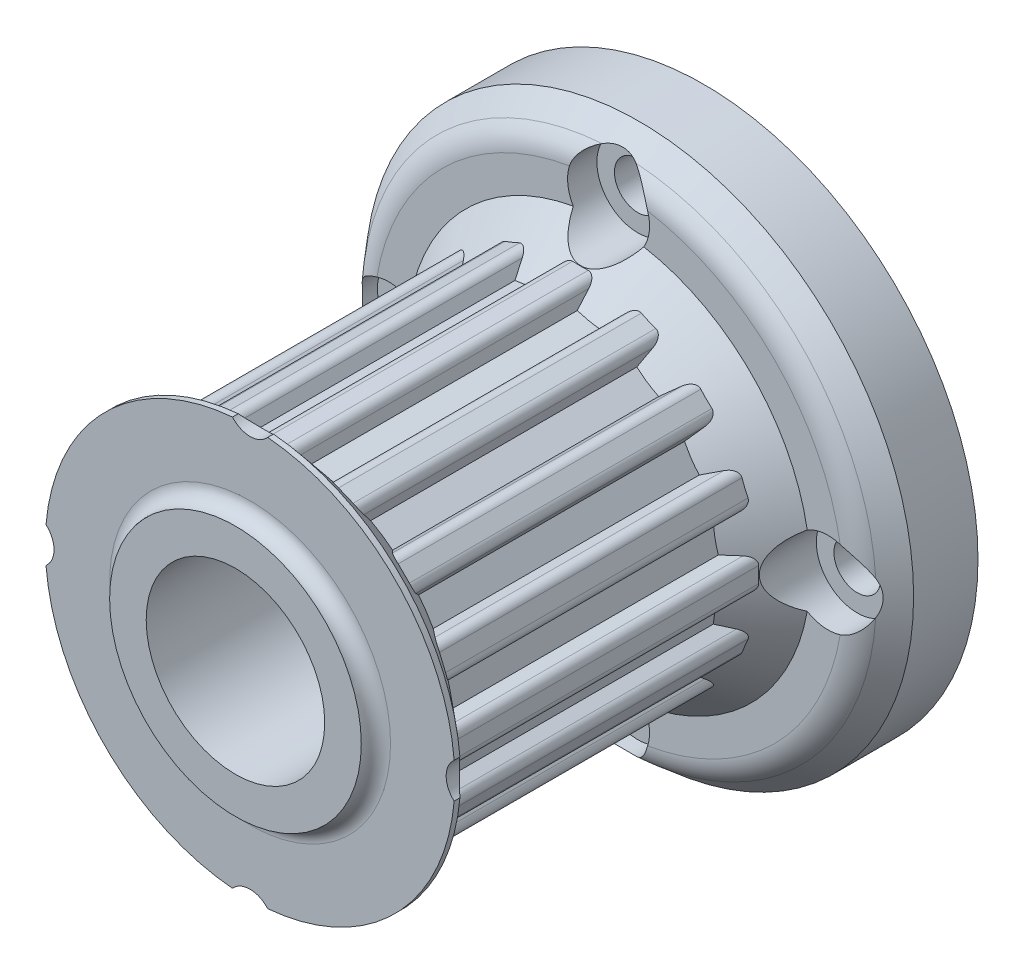
SolidWorks part; units mm, degrees
material "ABS"
ref_plane "Plan de face" through (0, 0, 0) normal (0, 0, 1) x (1, 0, 0)
ref_plane "Plan de dessus" through (0, 0, 0) normal (0, 1, 0) x (1, 0, 0)
ref_plane "Plan de droite" through (0, 0, 0) normal (1, 0, 0) x (0, 0, -1)
sketch "Esquisse1" plane through (0, 0, 0) normal (0, 0, 1) x (1, 0, 0)
  circle A0 centre (0, 0) radius 14
  dimension "D1" = 28
extrude "Boss.-Extru.1" add sketch "Esquisse1" along normal blind 28
sketch "Esquisse2" plane through (0, 0, 0) normal (0, 0, -1) x (-1, 0, 0)
  circle A0 centre (0, 0) radius 8.25
  circle A1 centre (0, 0) radius 14
  circle A2 centre (0, 0) radius 14 construction
  dimension "D1" = 16.5
extrude "Enlèv. mat.-Extru.1" cut sketch "Esquisse2" against normal blind 3.5
sketch "Esquisse3" plane through (0, 0, 0) normal (1, 0, 0) x (0, 0, -1)
  line L0 (-3.5, 14) -> (-28, 14) construction
  line L1 (-24.25, 14) -> (-7.25, 14)
  line L2 (-24.25, 14) -> (-24.25, 7.73)
  line L3 (-24.25, 7.73) -> (-7.25, 7.73)
  line L4 (-7.25, 14) -> (-7.25, 7.73)
  line L5 (-24.25, 14) -> (-7.25, 7.73) construction
  line L6 (-24.25, 7.73) -> (-7.25, 14) construction
  line L7 (-15.75, -14) -> (-15.75, 14) construction
  line L8 (-28, -14) -> (-3.5, -14) construction
  line L9 (-15.75, 0) -> (0, 0) construction
  point P4 (-15.75, 10.865)
  point P11 (0, 0)
  point P12 (-15.75, 0)
  dimension "D1" = 17
  dimension "D2" = 7.73
revolve "Enlèvement de matière-Révolution1" cut sketch "Esquisse3" angle 360 about L9
sketch "Esquisse4" plane through (0, 0, 0) normal (0, 0, -1) x (-1, 0, 0)
  circle A0 centre (0, 0) radius 3
  dimension "D1" = 6
extrude "Enlèv. mat.-Extru.2" cut sketch "Esquisse4" against normal through all
chamfer "Chanfrein1" distance 4 angle 40 2 edges at (14, 0, 7.25) (14, 0, 24.25) first distance on face at (-14, 0, 3.5) first distance on face at (7.73, 0, 24.25)
ref_plane "Plan1" through (0, 0, 5.25) normal (0, 0, 1) x (1, 0, 0)
sketch "Esquisse5" plane through (0, 0, 5.25) normal (0, 0, 1) x (1, 0, 0)
  line L0 (0, 0) -> (0, 12.73) construction
  line L1 (0, 0) -> (4.8716, 11.761) construction
  line L2 (0, 12.1872) -> (0.5089, 12.1872)
  line L3 (1.1017, 11.6799) -> (1.2239, 10.8985)
  line L4 (1.2239, 10.8985) -> (2.9901, 10.5515)
  line L5 (2.9901, 10.5515) -> (3.3975, 11.2265)
  line L6 (4.1408, 11.4708) -> (4.6619, 11.2549)
  line L7 (0, 0) -> (2.107, 10.725) construction
  line L8 (4.6619, 11.2549) -> (5.1321, 11.0601)
  line L9 (5.4856, 10.3646) -> (5.2995, 9.5959)
  line L10 (5.2995, 9.5959) -> (6.7985, 8.5995)
  line L11 (6.7985, 8.5995) -> (7.4332, 9.0671)
  line L12 (8.2134, 9.0084) -> (8.6122, 8.6095)
  line L13 (8.6122, 8.6095) -> (8.9721, 8.2497)
  line L14 (9.0325, 7.4718) -> (8.5664, 6.8329)
  line L15 (8.5664, 6.8329) -> (9.57, 5.3386)
  line L16 (9.57, 5.3386) -> (10.3353, 5.5278)
  line L17 (11.0336, 5.1749) -> (11.2495, 4.6538)
  line L18 (11.2495, 4.6538) -> (11.4442, 4.1836)
  line L19 (11.2024, 3.4418) -> (10.5272, 3.03)
  line L20 (10.5272, 3.03) -> (10.8826, 1.2654)
  line L21 (10.8826, 1.2654) -> (11.6621, 1.1473)
  line L22 (12.1722, 0.554) -> (12.1722, -0.01)
  line L23 (12.1722, -0.01) -> (12.1722, -0.5189)
  line L24 (11.6649, -1.1117) -> (10.8835, -1.2339)
  line L25 (10.8835, -1.2339) -> (10.5365, -3.0001)
  line L26 (10.5365, -3.0001) -> (11.2115, -3.4075)
  line L27 (11.4558, -4.1508) -> (11.2399, -4.6719)
  line L28 (11.2399, -4.6719) -> (11.0452, -5.1421)
  line L29 (10.3496, -5.4957) -> (9.581, -5.3095)
  line L30 (9.581, -5.3095) -> (8.5845, -6.8085)
  line L31 (8.5845, -6.8085) -> (9.0522, -7.4432)
  line L32 (8.9934, -8.2234) -> (8.5946, -8.6222)
  line L33 (8.5946, -8.6222) -> (8.2347, -8.9821)
  line L34 (7.4568, -9.0425) -> (6.8179, -8.5764)
  line L35 (6.8179, -8.5764) -> (5.3236, -9.58)
  line L36 (5.3236, -9.58) -> (5.5128, -10.3453)
  line L37 (5.16, -11.0436) -> (4.6389, -11.2595)
  line L38 (4.6389, -11.2595) -> (4.1687, -11.4542)
  line L39 (3.4269, -11.2124) -> (3.015, -10.5372)
  line L40 (3.015, -10.5372) -> (1.2504, -10.8926)
  line L41 (1.2504, -10.8926) -> (1.1323, -11.6721)
  line L42 (0.5391, -12.1822) -> (-0.025, -12.1822)
  line L43 (-0.025, -12.1822) -> (-0.5339, -12.1822)
  line L44 (-1.1267, -11.6749) -> (-1.2489, -10.8935)
  line L45 (-1.2489, -10.8935) -> (-3.0151, -10.5465)
  line L46 (-3.0151, -10.5465) -> (-3.4225, -11.2215)
  line L47 (-4.1658, -11.4658) -> (-4.6869, -11.2499)
  line L48 (-4.6869, -11.2499) -> (-5.1571, -11.0552)
  line L49 (-5.5106, -10.3596) -> (-5.3245, -9.591)
  line L50 (-5.3245, -9.591) -> (-6.8235, -8.5945)
  line L51 (-6.8235, -8.5945) -> (-7.4582, -9.0622)
  line L52 (-8.2384, -9.0034) -> (-8.6372, -8.6046)
  line L53 (-8.6372, -8.6046) -> (-8.9971, -8.2447)
  line L54 (-9.0575, -7.4668) -> (-8.5914, -6.8279)
  line L55 (-8.5914, -6.8279) -> (-9.5949, -5.3336)
  line L56 (-9.5949, -5.3336) -> (-10.3603, -5.5228)
  line L57 (-11.0586, -5.17) -> (-11.2745, -4.6489)
  line L58 (-11.2745, -4.6489) -> (-11.4692, -4.1787)
  line L59 (-11.2274, -3.4369) -> (-10.5522, -3.025)
  line L60 (-10.5522, -3.025) -> (-10.9076, -1.2604)
  line L61 (-10.9076, -1.2604) -> (-11.6871, -1.1423)
  line L62 (-12.1972, -0.5491) -> (-12.1972, 0.015)
  line L63 (-12.1972, 0.015) -> (-12.1972, 0.5239)
  line L64 (-11.6899, 1.1167) -> (-10.9085, 1.2389)
  line L65 (-10.9085, 1.2389) -> (-10.5615, 3.0051)
  line L66 (-10.5615, 3.0051) -> (-11.2365, 3.4125)
  line L67 (-11.4808, 4.1558) -> (-11.2649, 4.6769)
  line L68 (-11.2649, 4.6769) -> (-11.0702, 5.1471)
  line L69 (-10.3746, 5.5006) -> (-9.6059, 5.3145)
  line L70 (-9.6059, 5.3145) -> (-8.6095, 6.8135)
  line L71 (-8.6095, 6.8135) -> (-9.0772, 7.4482)
  line L72 (-9.0184, 8.2284) -> (-8.6195, 8.6272)
  line L73 (-8.6195, 8.6272) -> (-8.2597, 8.9871)
  line L74 (-7.4818, 9.0475) -> (-6.8429, 8.5814)
  line L75 (-6.8429, 8.5814) -> (-5.3486, 9.5849)
  line L76 (-5.3486, 9.5849) -> (-5.5378, 10.3503)
  line L77 (-5.185, 11.0486) -> (-4.6638, 11.2645)
  line L78 (-4.6638, 11.2645) -> (-4.1937, 11.4592)
  line L79 (-3.4518, 11.2174) -> (-3.04, 10.5422)
  line L80 (-3.04, 10.5422) -> (-1.2754, 10.8975)
  line L81 (-1.2754, 10.8975) -> (-1.1573, 11.6771)
  line L82 (-0.5641, 12.1872) -> (0, 12.1872)
  circle A0 centre (0, 0) radius 12.73 construction
  circle A1 centre (0, 0) radius 12.23 construction
  circle A2 centre (0, 0) radius 10.93 construction
  arc A3 (4.1408, 11.4708) -> (3.3975, 11.2265) centre (3.9112, 10.9164) ccw
  arc A4 (1.1017, 11.6799) -> (0.5089, 12.1872) centre (0.5089, 11.5872) ccw
  arc A5 (8.2134, 9.0084) -> (7.4332, 9.0671) centre (7.7891, 8.5841) ccw
  arc A6 (5.4856, 10.3646) -> (5.1321, 11.0601) centre (4.9025, 10.5058) ccw
  arc A7 (11.0336, 5.1749) -> (10.3353, 5.5278) centre (10.4793, 4.9453) ccw
  arc A8 (9.0325, 7.4718) -> (8.9721, 8.2497) centre (8.5478, 7.8254) ccw
  arc A9 (12.1722, 0.554) -> (11.6621, 1.1473) centre (11.5722, 0.554) ccw
  arc A10 (11.2024, 3.4418) -> (11.4442, 4.1836) centre (10.8899, 3.954) ccw
  arc A11 (11.4558, -4.1508) -> (11.2115, -3.4075) centre (10.9015, -3.9212) ccw
  arc A12 (11.6649, -1.1117) -> (12.1722, -0.5189) centre (11.5722, -0.5189) ccw
  arc A13 (8.9934, -8.2234) -> (9.0522, -7.4432) centre (8.5691, -7.7991) ccw
  arc A14 (10.3496, -5.4957) -> (11.0452, -5.1421) centre (10.4908, -4.9125) ccw
  arc A15 (5.16, -11.0436) -> (5.5128, -10.3453) centre (4.9304, -10.4893) ccw
  arc A16 (7.4568, -9.0425) -> (8.2347, -8.9821) centre (7.8104, -8.5578) ccw
  arc A17 (0.5391, -12.1822) -> (1.1323, -11.6721) centre (0.5391, -11.5822) ccw
  arc A18 (3.4269, -11.2124) -> (4.1687, -11.4542) centre (3.9391, -10.8999) ccw
  arc A19 (-4.1658, -11.4658) -> (-3.4225, -11.2215) centre (-3.9362, -10.9115) ccw
  arc A20 (-1.1267, -11.6749) -> (-0.5339, -12.1822) centre (-0.5339, -11.5822) ccw
  arc A21 (-8.2384, -9.0034) -> (-7.4582, -9.0622) centre (-7.8141, -8.5792) ccw
  arc A22 (-5.5106, -10.3596) -> (-5.1571, -11.0552) centre (-4.9275, -10.5009) ccw
  arc A23 (-11.0586, -5.17) -> (-10.3603, -5.5228) centre (-10.5043, -4.9404) ccw
  arc A24 (-9.0575, -7.4668) -> (-8.9971, -8.2447) centre (-8.5728, -7.8204) ccw
  arc A25 (-12.1972, -0.5491) -> (-11.6871, -1.1423) centre (-11.5972, -0.5491) ccw
  arc A26 (-11.2274, -3.4369) -> (-11.4692, -4.1787) centre (-10.9149, -3.9491) ccw
  arc A27 (-11.4808, 4.1558) -> (-11.2365, 3.4125) centre (-10.9264, 3.9262) ccw
  arc A28 (-11.6899, 1.1167) -> (-12.1972, 0.5239) centre (-11.5972, 0.5239) ccw
  arc A29 (-9.0184, 8.2284) -> (-9.0772, 7.4482) centre (-8.5941, 7.8041) ccw
  arc A30 (-10.3746, 5.5006) -> (-11.0702, 5.1471) centre (-10.5158, 4.9175) ccw
  arc A31 (-5.185, 11.0486) -> (-5.5378, 10.3503) centre (-4.9553, 10.4943) ccw
  arc A32 (-7.4818, 9.0475) -> (-8.2597, 8.9871) centre (-7.8354, 8.5628) ccw
  arc A33 (-0.5641, 12.1872) -> (-1.1573, 11.6771) centre (-0.5641, 11.5872) ccw
  arc A34 (-3.4518, 11.2174) -> (-4.1937, 11.4592) centre (-3.964, 10.9049) ccw
  circle A36 centre (0, 0) radius 7.0444
  point P2 (6.049, 9.0977)
  point P15 (3.6641, 11.6682)
  point P19 (1.0224, 12.1872)
  point P172 (-0.0125, 0.0025)
  dimension "D1" = 25.46
  dimension "D8" = 0.6
  dimension "D2" = 22.5
  dimension "D3" = 0.5
  dimension "D4" = 1.3
  dimension "D5" = 20
  dimension "D6" = 20
  dimension "D7" = 1.8
  dimension "D9" = 16
sketch "Esquisse6" plane through (0, 0, 0) normal (0, 0, -1) x (-1, 0, 0)
  circle A0 centre (0, 0) radius 6.1
  dimension "D1" = 12.2
extrude "Enlèv. mat.-Extru.4" cut sketch "Esquisse6" against normal through all
sketch "Esquisse7" plane through (0, 0, 0) normal (0, 0, -1) x (-1, 0, 0)
  circle A0 centre (0, 0) radius 8.25 construction
  circle A1 centre (0, 0) radius 8.25
  circle A2 centre (0, 0) radius 18.75
  dimension "D1" = 37.5
extrude "Boss.-Extru.2" add sketch "Esquisse7" against normal up to surface (3.5 mm away) up to face at (-13.7902, 0, 3.5)
sketch "Esquisse8" plane through (0, 0, 0) normal (0, 0, -1) x (-1, 0, 0)
  circle A0 centre (0, 0) radius 15 construction
  circle A1 centre (0, 15) radius 1.6
  circle A2 centre (15, 0) radius 1.6
  circle A3 centre (0, -15) radius 1.6
  circle A4 centre (-15, 0) radius 1.6
  point P13 (0, 0)
  dimension "D1" = 30
  dimension "D2" = 3.2
  dimension "D3" = 4
extrude "Enlèv. mat.-Extru.5" cut sketch "Esquisse8" against normal through all
sketch "Esquisse9" plane through (0, 0, 3.5) normal (0, 0, 1) x (1, 0, 0)
  circle A0 centre (15, 0) radius 2.8
  circle A1 centre (0, 0) radius 15 construction
  circle A2 centre (0, -15) radius 2.8
  circle A3 centre (-15, 0) radius 2.8
  circle A4 centre (0, 15) radius 2.8
  point P16 (0, 0)
  dimension "D1" = 5.6
  dimension "D2" = 4
extrude "Enlèv. mat.-Extru.6" cut sketch "Esquisse9" along normal blind 5.5 and the other way blind 2
sketch "Esquisse10" plane through (0, 0, 28) normal (0, 0, 1) x (1, 0, 0)
  circle A0 centre (0, 0) radius 8.6
  circle A1 centre (0, 0) radius 6.1 construction
  circle A2 centre (0, 0) radius 6.1
  dimension "D1" = 2.5
extrude "Boss.-Extru.3" add sketch "Esquisse10" along normal blind 1
sketch "Esquisse11" plane through (0, 0, 0) normal (0, 0, -1) x (-1, 0, 0)
  circle A0 centre (-15, 0) radius 1.6 construction
  circle A1 centre (0, 0) radius 18.75
  circle A2 centre (0, 0) radius 18.75
  circle A3 centre (0, 15) radius 1.6 construction
  circle A4 centre (15, 0) radius 1.6 construction
  circle A5 centre (0, -15) radius 1.6 construction
  circle A6 centre (-15, 0) radius 1.6
  circle A7 centre (0, 15) radius 1.6
  circle A8 centre (15, 0) radius 1.6
  circle A9 centre (0, -15) radius 1.6
  dimension "D1" = 0
extrude "Boss.-Extru.4" add sketch "Esquisse11" along normal blind 3
sketch "Esquisse12" plane through (0, 0, -3) normal (0, 0, -1) x (-1, 0, 0)
  circle A0 centre (0, 0) radius 1.6
  dimension "D1" = 3.2
extrude "Enlèv. mat.-Extru.7" cut sketch "Esquisse12" against normal blind 32
extrude "Boss.-Extru.5" add sketch "Esquisse5" along normal blind 21
chamfer "Chanfrein2" distance 2.1 angle 40 1 edges at (-18.75, 0, 3.5) first distance on face at (-18.75, 0, 3.5)
fillet "Congé1" radius 2 4 edges at (-12.0123, 12.0123, 3.5) (-12.0123, -12.0123, 3.5) (12.0123, -12.0123, 3.5) (12.0123, 12.0123, 3.5)
fillet "Congé4" radius 1 1 edges at (8.6, 0, 28)
equation "\"A\"= 26"
equation "\"E\"= 20.5"
equation "\"C\"= 6"
equation "\"B\"= 16.5"
equation "\"Dp\"= 25.46'Diamètre primitif"
equation "\"Df\"= 28'Diamètre extérieur"
equation "\"Teeth\"= 16'Nombre de dents"
equation "\"L\"= 15'Largeur courroie"
equation "\"D1@Enlèv. mat.-Extru.1\"=\"A\"-\"E\"-2"
equation "\"D1@Esquisse3\"=\"L\"+2"
equation "\"D2@Esquisse3\"=\"Dp\"/2-5"
equation "\"D1@Esquisse5\"=\"Dp\""
equation "\"D2@Esquisse5\"=360/\"Teeth\""
